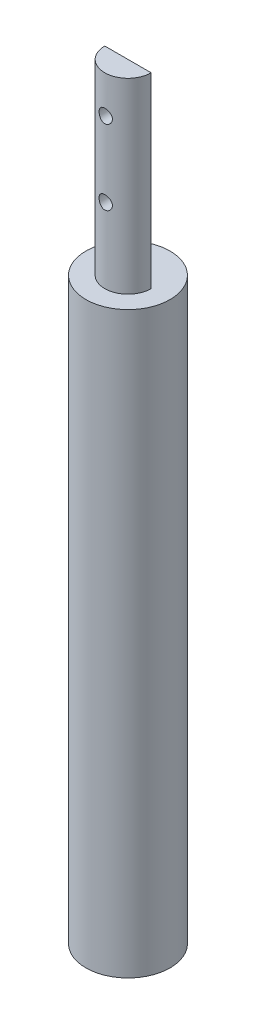
SolidWorks part; units mm, degrees
ref_plane "Front Plane" through (0, 0, 0) normal (0, 0, 1) x (1, 0, 0)
ref_plane "Top Plane" through (0, 0, 0) normal (0, 1, 0) x (1, 0, 0)
ref_plane "Right Plane" through (0, 0, 0) normal (1, 0, 0) x (0, 0, -1)
sketch "Sketch1" plane through (0, 0, 0) normal (0, 1, 0) x (1, 0, 0)
  circle A0 centre (0, 0) radius 7.1438
  dimension "D1" = 14.2875
extrude "Boss-Extrude1" add sketch "Sketch1" along normal blind 130.048
hole_wizard "M10x1.0 Tapped Hole1" positions "Sketch3" profile "Sketch2" tap size "M10x1.0" standard "Ansi Metric"
sketch "Sketch3" plane through (0, 0, 0) normal (0, -1, 0) x (1, 0, 0)
  point P1 (0, 0)
sketch "Sketch2" plane through (0, 0, 0) normal (1, 0, 0) x (0, 0, -1)
  line L0 (0, 0) -> (0, 17.7039)
  line L1 (0, 17.7039) -> (4.5, 15)
  line L2 (4.5, 15) -> (4.5, 0)
  line L5 (4.5, 0) -> (0, 0)
  line L10 (0, 17.7039) -> (-4.5, 15) construction
  line L11 (0, -6.35) -> (0, 107.95) construction
  dimension "Tap Drill Dia." = 9
  dimension "Tap Drill Depth" = 15
  dimension "Drill Angle" = 118
cosmetic thread "Hole Thread1" parameters "D1"=15, "D2"=10
sketch "Sketch4" plane through (0, 130.048, 0) normal (0, 1, 0) x (1, 0, 0)
  circle A0 centre (0, 0) radius 3.937
  circle A1 centre (0, 0) radius 7.1438
  dimension "D1" = 7.874
extrude "Cut-Extrude1" cut sketch "Sketch4" against normal blind 31.75
sketch "Sketch5" plane through (0, 130.048, 0) normal (0, 1, 0) x (1, 0, 0)
  line L0 (-3.937, 0) -> (3.937, 0)
  line L1 (3.937, 0) -> (3.937, 3.937)
  line L2 (3.937, 3.937) -> (-3.937, 3.937)
  line L3 (-3.937, 3.937) -> (-3.937, 0)
  circle A0 centre (0, 0) radius 3.937 construction
  circle A1 centre (0, 0) radius 3.937 construction
extrude "Cut-Extrude2" cut sketch "Sketch5" against normal up to surface (31.75 mm away) up to face at (0, 98.298, 3.937)
sketch "Sketch6" plane through (0, 0, 0) normal (0, 0, -1) x (-1, 0, 0)
  line L0 (0, 130.048) -> (0, 98.298) construction
  line L1 (3.937, 130.048) -> (-3.937, 130.048) construction
  line L2 (-3.937, 98.298) -> (3.937, 98.298) construction
  point P6 (0, 123.698)
  point P7 (0, 110.998)
  dimension "D1" = 6.35
  dimension "D2" = 12.7
hole_wizard "#4-40 Tapped Hole1" positions "Sketch8" profile "Sketch7" tap size "#4-40" standard "Ansi Inch" end condition through all
sketch "Sketch8" plane through (0, 0, 0) normal (0, 0, -1) x (-1, 0, 0)
  point P1 (0, 110.998)
  point P4 (0, 123.698)
sketch "Sketch7" plane through (0, 110.998, 0) normal (1, 0, 0) x (0, 1, 0)
  line L0 (0, 0) -> (0, 7.1438)
  line L1 (0, 7.1438) -> (1.1303, 7.1438)
  line L2 (1.1303, 7.1438) -> (1.1303, 0)
  line L5 (1.1303, 0) -> (0, 0)
  line L11 (0, -6.35) -> (0, 107.95) construction
  dimension "Thru Tap Drill Dia." = 2.2606
  dimension "Thru Tap Drill Depth" = 7.1438
cosmetic thread "Hole Thread2" parameters "D2"=2.8448
cosmetic thread "Hole Thread3" parameters "D2"=2.8448
